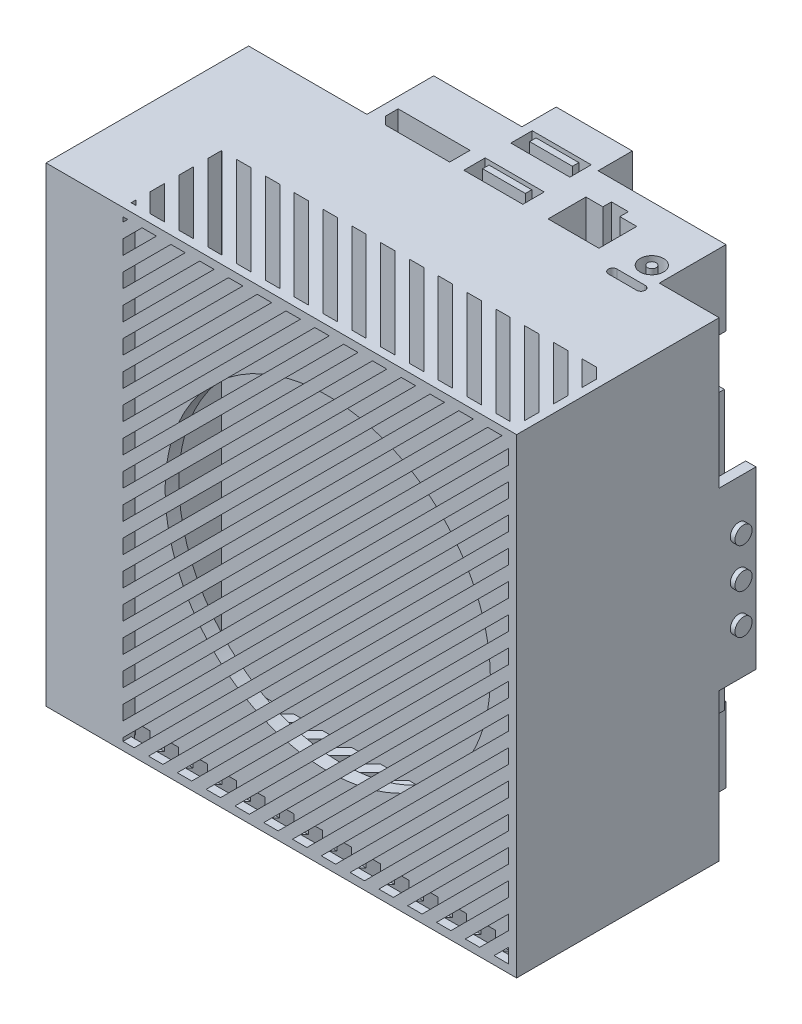
SolidWorks part; units mm, degrees
ref_plane "Plan de face" through (0, 0, 0) normal (0, 0, 1) x (1, 0, 0)
ref_plane "Plan de dessus" through (0, 0, 0) normal (0, 1, 0) x (1, 0, 0)
ref_plane "Plan de droite" through (0, 0, 0) normal (1, 0, 0) x (0, 0, -1)
sketch "Esquisse1" plane through (0, 0, 0) normal (0, 0, 1) x (1, 0, 0)
  line L0 (-110, 0) -> (0, 0)
  line L1 (0, 0) -> (0, -110)
  line L2 (0, -110) -> (-110, -110)
  line L3 (-110, -110) -> (-110, 0)
  line L4 (-107.6, -55) -> (-110, -55) construction
  line L5 (-107.6, -17.5) -> (-2.4, -17.5)
  line L6 (-107.6, -17.5) -> (-107.6, -92.5)
  line L7 (-107.6, -92.5) -> (-2.4, -92.5)
  line L8 (-2.4, -17.5) -> (-2.4, -92.5)
  line L9 (-2.4, -55) -> (0, -55) construction
  line L10 (-87.5, -9) -> (-87.5, 0) construction
  line L11 (-87.5, -101) -> (-87.5, -110) construction
  circle A0 centre (-87.5, -9) radius 3.1
  circle A1 centre (-8.5, -9) radius 3.1
  circle A2 centre (-87.5, -101) radius 3.1
  circle A3 centre (-8.5, -101) radius 3.1
  dimension "D7" = 6.2
  dimension "D1" = 110
  dimension "D2" = 2.4
  dimension "D3" = 17.5
  dimension "D4" = 9
  dimension "D5" = 8.5
  dimension "D6" = 79
extrude "Boss.-Extru.1" add sketch "Esquisse1" along normal blind 23.6
sketch "Esquisse3" plane through (0, 0, 23.6) normal (0, 0, 1) x (1, 0, 0)
  line L0 (0, -110) -> (0, 0) construction
  line L1 (-110, -110) -> (0, -110) construction
  line L2 (-110, 0) -> (-110, -110) construction
  line L3 (0, 0) -> (-110, 0) construction
  line L4 (0, -110) -> (0, 0)
  line L5 (-110, -110) -> (0, -110)
  line L6 (-110, 0) -> (-110, -110)
  line L7 (0, 0) -> (-110, 0)
extrude "Boss.-Extru.2" add sketch "Esquisse3" along normal blind 47.35
sketch "Esquisse15" plane through (0, 0, 23.6) normal (0, 0, -1) x (-1, 0, 0)
  circle A0 centre (87.5, -9) radius 1.25
  circle A1 centre (8.5, -9) radius 1.25
  circle A2 centre (8.5, -101) radius 1.25
  circle A3 centre (87.5, -101) radius 1.25
  dimension "D1" = 2.5
extrude "Enlèv. mat.-Extru.11" cut sketch "Esquisse15" against normal blind 10
sketch "Esquisse4" plane through (0, 0, 0) normal (0, 0, -1) x (-1, 0, 0)
  line L0 (0, -110) -> (0, 0) construction
  line L1 (0, -34.5) -> (2.4, -34.5)
  line L2 (0, -34.5) -> (0, -75.5)
  line L3 (0, -75.5) -> (2.4, -75.5)
  line L4 (2.4, -34.5) -> (2.4, -75.5)
  line L5 (2.4, -92.5) -> (2.4, -17.5) construction
  point P8 (2.4, -55)
  point P9 (0, -55)
  dimension "D1" = 41
extrude "Enlèv. mat.-Extru.1" cut sketch "Esquisse4" against normal blind 15
sketch "Esquisse5" plane through (0, 0, 0) normal (1, 0, 0) x (0, 0, -1)
  line L0 (-19, -45.7) -> (-19, -55) construction
  line L1 (-19, -55) -> (-19, -64.3) construction
  line L2 (-15, -34.5) -> (-15, -75.5) construction
  circle A0 centre (-19, -45.7) radius 2
  circle A1 centre (-19, -55) radius 2
  circle A2 centre (-19, -64.3) radius 2
  point P8 (-15, -55)
  dimension "D1" = 4
  dimension "D2" = 9.3
  dimension "D3" = 4
extrude "Boss.-Extru.3" add sketch "Esquisse5" along normal blind 1.1
sketch "Esquisse6" plane through (0, 0, 23.6) normal (0, 0, -1) x (-1, 0, 0)
  line L1 (7.4, -22.5) -> (102.6, -22.5)
  line L2 (7.4, -22.5) -> (7.4, -87.5)
  line L3 (7.4, -87.5) -> (102.6, -87.5)
  line L4 (102.6, -22.5) -> (102.6, -87.5)
  line L5 (55, -22.5) -> (55, -17.5) construction
  line L6 (2.4, -17.5) -> (107.6, -17.5) construction
  line L7 (102.6, -55) -> (107.6, -55) construction
  line L8 (107.6, -17.5) -> (107.6, -92.5) construction
  line L9 (2.4, -55) -> (7.4, -55) construction
  line L10 (2.4, -92.5) -> (2.4, -17.5) construction
  line L11 (55, -87.5) -> (55, -92.5) construction
  line L12 (107.6, -92.5) -> (2.4, -92.5) construction
  dimension "D1" = 5
extrude "Boss.-Extru.4" add sketch "Esquisse6" along normal up to surface (8.6 mm away) up to face at (-1.2, -55, 15)
sketch "Esquisse7" plane through (0, 0, 70.95) normal (0, 0, 1) x (1, 0, 0)
  line L0 (-1.9, -108.1) -> (-1.9, -110) construction
  line L1 (-1.9, -108.1) -> (-92, -108.1) construction
  line L2 (-1.9, -108.1) -> (-1.9, -1.9) construction
  line L3 (-1.9, -1.9) -> (-92, -1.9) construction
  line L4 (-92, -108.1) -> (-92, -1.9) construction
  line L5 (-110, -110) -> (0, -110) construction
  line L6 (-1.9, -108.1) -> (0, -108.1) construction
  line L7 (0, -110) -> (0, 0) construction
  line L8 (-1.9, -1.9) -> (-1.9, 0) construction
  line L9 (0, 0) -> (-110, 0) construction
  line L10 (-1.9, -1.9) -> (0, -1.9) construction
  line L11 (-110, 0) -> (-110, -110) construction
  line L12 (-1.9, -101.3683) -> (-8.6317, -108.1)
  line L13 (-1.9, -101.3683) -> (-1.9, -98.0025)
  line L14 (-1.9, -98.0025) -> (-11.9975, -108.1)
  line L15 (-11.9975, -108.1) -> (-8.6317, -108.1)
  line L16 (-1.9, -108.1) -> (-1.9, -104.7342)
  line L17 (-1.9, -104.7342) -> (-5.2658, -108.1)
  line L18 (-5.2658, -108.1) -> (-1.9, -108.1)
  line L19 (-1.9, -108.1) -> (-3.5829, -106.4171) construction
  line L20 (-3.5829, -106.4171) -> (-5.2658, -104.7342) construction
  line L21 (-5.2658, -104.7342) -> (-6.9487, -103.0513) construction
  line L22 (-6.9487, -103.0513) -> (-8.6317, -101.3683) construction
  line L23 (-8.6317, -101.3683) -> (-10.3146, -99.6854) construction
  line L24 (-1.9, -94.6367) -> (-15.3633, -108.1)
  line L25 (-15.3633, -108.1) -> (-18.7291, -108.1)
  line L26 (-18.7291, -108.1) -> (-1.9, -91.2709)
  line L27 (-1.9, -91.2709) -> (-1.9, -94.6367)
  line L28 (-1.9, -87.905) -> (-22.095, -108.1)
  line L29 (-22.095, -108.1) -> (-25.4608, -108.1)
  line L30 (-25.4608, -108.1) -> (-1.9, -84.5392)
  line L31 (-1.9, -84.5392) -> (-1.9, -87.905)
  line L32 (-1.9, -81.1734) -> (-28.8266, -108.1)
  line L33 (-28.8266, -108.1) -> (-32.1925, -108.1)
  line L34 (-32.1925, -108.1) -> (-1.9, -77.8075)
  line L35 (-1.9, -77.8075) -> (-1.9, -81.1734)
  line L36 (-1.9, -74.4417) -> (-35.5583, -108.1)
  line L37 (-35.5583, -108.1) -> (-38.9241, -108.1)
  line L38 (-38.9241, -108.1) -> (-1.9, -71.0759)
  line L39 (-1.9, -71.0759) -> (-1.9, -74.4417)
  line L40 (-1.9, -67.7101) -> (-42.2899, -108.1)
  line L41 (-42.2899, -108.1) -> (-45.6558, -108.1)
  line L42 (-45.6558, -108.1) -> (-1.9, -64.3442)
  line L43 (-1.9, -64.3442) -> (-1.9, -67.7101)
  line L44 (-1.9, -60.9784) -> (-49.0216, -108.1)
  line L45 (-49.0216, -108.1) -> (-52.3874, -108.1)
  line L46 (-52.3874, -108.1) -> (-1.9, -57.6126)
  line L47 (-1.9, -57.6126) -> (-1.9, -60.9784)
  line L48 (-1.9, -54.2467) -> (-55.7533, -108.1)
  line L49 (-55.7533, -108.1) -> (-59.1191, -108.1)
  line L50 (-59.1191, -108.1) -> (-1.9, -50.8809)
  line L51 (-1.9, -50.8809) -> (-1.9, -54.2467)
  line L52 (-10.3146, -99.6854) -> (-11.9975, -98.0025) construction
  line L53 (-11.9975, -98.0025) -> (-13.6804, -96.3196) construction
  line L54 (-13.6804, -96.3196) -> (-15.3633, -94.6367) construction
  line L55 (-15.3633, -94.6367) -> (-17.0462, -92.9538) construction
  line L56 (-17.0462, -92.9538) -> (-18.7291, -91.2709) construction
  line L57 (-18.7291, -91.2709) -> (-20.4121, -89.5879) construction
  line L58 (-20.4121, -89.5879) -> (-22.095, -87.905) construction
  line L59 (-22.095, -87.905) -> (-23.7779, -86.2221) construction
  line L60 (-23.7779, -86.2221) -> (-25.4608, -84.5392) construction
  line L61 (-25.4608, -84.5392) -> (-27.1437, -82.8563) construction
  line L62 (-27.1437, -82.8563) -> (-28.8266, -81.1734) construction
  line L63 (-28.8266, -81.1734) -> (-30.5095, -79.4905) construction
  line L64 (-1.9, -47.5151) -> (-62.4849, -108.1)
  line L65 (-62.4849, -108.1) -> (-65.8507, -108.1)
  line L66 (-65.8507, -108.1) -> (-1.9, -44.1493)
  line L67 (-1.9, -44.1493) -> (-1.9, -47.5151)
  line L68 (-69.2166, -108.1) -> (-1.9, -40.7834)
  line L69 (-1.9, -40.7834) -> (-1.9, -37.4176)
  line L70 (-1.9, -37.4176) -> (-72.5824, -108.1)
  line L71 (-72.5824, -108.1) -> (-69.2166, -108.1)
  line L72 (-1.9, -34.0518) -> (-75.9482, -108.1)
  line L73 (-75.9482, -108.1) -> (-79.3141, -108.1)
  line L74 (-79.3141, -108.1) -> (-1.9, -30.6859)
  line L75 (-1.9, -30.6859) -> (-1.9, -34.0518)
  line L76 (-82.6799, -108.1) -> (-86.0457, -108.1)
  line L77 (-86.0457, -108.1) -> (-1.9, -23.9543)
  line L78 (-1.9, -23.9543) -> (-1.9, -27.3201)
  line L79 (-1.9, -27.3201) -> (-82.6799, -108.1)
  line L81 (-92, -107.3226) -> (-1.9, -17.2226)
  line L82 (-1.9, -17.2226) -> (-1.9, -20.5885)
  line L83 (-1.9, -20.5885) -> (-89.4115, -108.1)
  line L84 (-92, -103.9568) -> (-92, -100.591)
  line L85 (-92, -100.591) -> (-1.9, -10.491)
  line L86 (-1.9, -10.491) -> (-1.9, -13.8568)
  line L87 (-1.9, -13.8568) -> (-92, -103.9568)
  line L88 (-30.5095, -79.4905) -> (-32.1925, -77.8075) construction
  line L89 (-32.1925, -77.8075) -> (-33.8754, -76.1246) construction
  line L90 (-33.8754, -76.1246) -> (-35.5583, -74.4417) construction
  line L91 (-35.5583, -74.4417) -> (-37.2412, -72.7588) construction
  line L92 (-37.2412, -72.7588) -> (-38.9241, -71.0759) construction
  line L93 (-38.9241, -71.0759) -> (-40.607, -69.393) construction
  line L94 (-40.607, -69.393) -> (-42.2899, -67.7101) construction
  line L95 (-42.2899, -67.7101) -> (-43.9729, -66.0271) construction
  line L96 (-43.9729, -66.0271) -> (-45.6558, -64.3442) construction
  line L97 (-45.6558, -64.3442) -> (-47.3387, -62.6613) construction
  line L98 (-47.3387, -62.6613) -> (-49.0216, -60.9784) construction
  line L99 (-49.0216, -60.9784) -> (-50.7045, -59.2955) construction
  line L100 (-89.4115, -108.1) -> (-92, -108.1)
  line L101 (-92, -108.1) -> (-92, -107.3226)
  line L102 (-92, -97.2252) -> (-1.9, -7.1252)
  line L103 (-1.9, -7.1252) -> (-1.9, -3.7593)
  line L104 (-1.9, -3.7593) -> (-92, -93.8593)
  line L105 (-92, -93.8593) -> (-92, -97.2252)
  line L106 (-50.7045, -59.2955) -> (-52.3874, -57.6126) construction
  line L107 (-52.3874, -57.6126) -> (-54.0703, -55.9297) construction
  line L108 (-92, -90.4935) -> (-3.4065, -1.9)
  line L109 (-3.4065, -1.9) -> (-6.7723, -1.9)
  line L110 (-6.7723, -1.9) -> (-92, -87.1277)
  line L111 (-92, -87.1277) -> (-92, -90.4935)
  line L112 (-92, -83.7618) -> (-10.1382, -1.9)
  line L113 (-10.1382, -1.9) -> (-13.504, -1.9)
  line L114 (-13.504, -1.9) -> (-92, -80.396)
  line L115 (-92, -80.396) -> (-92, -83.7618)
  line L116 (-92, -77.0302) -> (-16.8698, -1.9)
  line L117 (-16.8698, -1.9) -> (-20.2356, -1.9)
  line L118 (-20.2356, -1.9) -> (-92, -73.6644)
  line L119 (-92, -73.6644) -> (-92, -77.0302)
  line L120 (-92, -70.2985) -> (-23.6015, -1.9)
  line L121 (-23.6015, -1.9) -> (-26.9673, -1.9)
  line L122 (-26.9673, -1.9) -> (-92, -66.9327)
  line L123 (-92, -66.9327) -> (-92, -70.2985)
  line L124 (-92, -63.5669) -> (-30.3331, -1.9)
  line L125 (-30.3331, -1.9) -> (-33.699, -1.9)
  line L126 (-33.699, -1.9) -> (-92, -60.201)
  line L127 (-92, -60.201) -> (-92, -63.5669)
  line L128 (-92, -56.8352) -> (-37.0648, -1.9)
  line L129 (-37.0648, -1.9) -> (-40.4306, -1.9)
  line L130 (-40.4306, -1.9) -> (-92, -53.4694)
  line L131 (-92, -53.4694) -> (-92, -56.8352)
  line L132 (-92, -50.1036) -> (-43.7964, -1.9)
  line L133 (-43.7964, -1.9) -> (-47.1623, -1.9)
  line L134 (-47.1623, -1.9) -> (-92, -46.7377)
  line L135 (-92, -46.7377) -> (-92, -50.1036)
  line L136 (-54.0703, -55.9297) -> (-55.7533, -54.2467) construction
  line L137 (-55.7533, -54.2467) -> (-57.4362, -52.5638) construction
  line L138 (-57.4362, -52.5638) -> (-59.1191, -50.8809) construction
  line L139 (-59.1191, -50.8809) -> (-60.802, -49.198) construction
  line L140 (-60.802, -49.198) -> (-62.4849, -47.5151) construction
  line L141 (-62.4849, -47.5151) -> (-64.1678, -45.8322) construction
  line L142 (-64.1678, -45.8322) -> (-65.8507, -44.1493) construction
  line L143 (-65.8507, -44.1493) -> (-67.5337, -42.4663) construction
  line L144 (-67.5337, -42.4663) -> (-69.2166, -40.7834) construction
  line L145 (-69.2166, -40.7834) -> (-70.8995, -39.1005) construction
  line L146 (-70.8995, -39.1005) -> (-72.5824, -37.4176) construction
  line L147 (-72.5824, -37.4176) -> (-74.2653, -35.7347) construction
  line L148 (-74.2653, -35.7347) -> (-75.9482, -34.0518) construction
  line L149 (-75.9482, -34.0518) -> (-77.6311, -32.3689) construction
  line L150 (-92, -43.3719) -> (-50.5281, -1.9)
  line L151 (-50.5281, -1.9) -> (-53.8939, -1.9)
  line L152 (-53.8939, -1.9) -> (-92, -40.0061)
  line L153 (-92, -40.0061) -> (-92, -43.3719)
  line L154 (-92, -36.6402) -> (-57.2598, -1.9)
  line L155 (-57.2598, -1.9) -> (-60.6256, -1.9)
  line L156 (-60.6256, -1.9) -> (-92, -33.2744)
  line L157 (-92, -33.2744) -> (-92, -36.6402)
  line L158 (-92, -29.9086) -> (-63.9914, -1.9)
  line L159 (-63.9914, -1.9) -> (-67.3572, -1.9)
  line L160 (-67.3572, -1.9) -> (-92, -26.5428)
  line L161 (-92, -26.5428) -> (-92, -29.9086)
  line L162 (-92, -23.1769) -> (-70.7231, -1.9)
  line L163 (-70.7231, -1.9) -> (-74.0889, -1.9)
  line L164 (-74.0889, -1.9) -> (-92, -19.8111)
  line L165 (-92, -19.8111) -> (-92, -23.1769)
  line L166 (-92, -13.0794) -> (-80.8206, -1.9)
  line L167 (-80.8206, -1.9) -> (-77.4547, -1.9)
  line L168 (-77.4547, -1.9) -> (-92, -16.4453)
  line L169 (-92, -16.4453) -> (-92, -13.0794)
  line L170 (-92, -9.7136) -> (-84.1864, -1.9)
  line L171 (-84.1864, -1.9) -> (-87.5522, -1.9)
  line L172 (-87.5522, -1.9) -> (-92, -6.3478)
  line L173 (-92, -6.3478) -> (-92, -9.7136)
  line L174 (-77.6311, -32.3689) -> (-79.3141, -30.6859) construction
  line L175 (-79.3141, -30.6859) -> (-80.997, -29.003) construction
  line L176 (-80.997, -29.003) -> (-82.6799, -27.3201) construction
  line L177 (-82.6799, -27.3201) -> (-84.3628, -25.6372) construction
  line L178 (-84.3628, -25.6372) -> (-86.0457, -23.9543) construction
  line L179 (-86.0457, -23.9543) -> (-87.7286, -22.2714) construction
  line L180 (-79.6786, -14.2214) -> (-81.3615, -12.5385) construction
  line L181 (-81.3615, -12.5385) -> (-83.0444, -10.8556) construction
  line L182 (-83.0444, -10.8556) -> (-84.7274, -9.1726) construction
  line L183 (-84.7274, -9.1726) -> (-86.4103, -7.4897) construction
  line L184 (-86.4103, -7.4897) -> (-88.0932, -5.8068) construction
  line L185 (-88.0932, -5.8068) -> (-89.7761, -4.1239) construction
  line L186 (-92, -1.9) -> (-92, -2.982)
  line L187 (-92, -2.982) -> (-90.918, -1.9)
  line L188 (-90.918, -1.9) -> (-92, -1.9)
  line L189 (-92, -1.9) -> (-91.459, -2.441) construction
  line L190 (-91.459, -2.441) -> (-89.7761, -4.1239) construction
  point P32 (-8.6317, -101.3683)
  point P34 (-10.3146, -99.6854)
  dimension "D1" = 1.9
  dimension "D2" = 18
  dimension "D3" = 45
  dimension "D4" = 2.38
extrude "Enlèv. mat.-Extru.2" cut sketch "Esquisse7" against normal blind 2.8
sketch "Esquisse8" plane through (0, 0, 68.15) normal (0, 0, 1) x (1, 0, 0)
  line L2 (0, -110) -> (0, 0) construction
  circle A0 centre (-46.95, -55) radius 38
  point P3 (0, -55)
  dimension "D1" = 76
  dimension "D2" = 46.95
extrude "Enlèv. mat.-Extru.3" cut sketch "Esquisse8" against normal blind 20.14
sketch "Esquisse9" plane through (0, 0, 0) normal (0, 1, 0) x (1, 0, 0)
  line L0 (-1.9, -69.05) -> (-1.9, -47.95) construction
  line L1 (-1.9, -47.95) -> (-92, -47.95) construction
  line L2 (-92, -47.95) -> (-92, -69.05) construction
  line L3 (-92, -69.05) -> (-1.9, -69.05) construction
  line L4 (0, -70.95) -> (-110, -70.95) construction
  line L5 (-1.9, -69.05) -> (0, -69.05) construction
  line L6 (0, -70.95) -> (0, 0) construction
  line L7 (-1.9, -69.05) -> (-1.9, -70.95) construction
  line L8 (-84.1864, -70.95) -> (-87.5522, -70.95) construction
  line L9 (-77.4547, -70.95) -> (-80.8206, -70.95) construction
  line L10 (-70.7231, -70.95) -> (-74.0889, -70.95) construction
  line L11 (-63.9914, -70.95) -> (-67.3572, -70.95) construction
  line L12 (-57.2598, -70.95) -> (-60.6256, -70.95) construction
  line L13 (-50.5281, -70.95) -> (-53.8939, -70.95) construction
  line L14 (-43.7964, -70.95) -> (-47.1623, -70.95) construction
  line L15 (-37.0648, -70.95) -> (-40.4306, -70.95) construction
  line L16 (-30.3331, -70.95) -> (-33.699, -70.95) construction
  line L17 (-23.6015, -70.95) -> (-26.9673, -70.95) construction
  line L18 (-16.8698, -70.95) -> (-20.2356, -70.95) construction
  line L19 (-10.1382, -70.95) -> (-13.504, -70.95) construction
  line L20 (-3.4065, -70.95) -> (-6.7723, -70.95) construction
  line L21 (-84.1864, -70.95) -> (-87.5522, -70.95) construction
  line L22 (-77.4547, -70.95) -> (-80.8206, -70.95) construction
  line L23 (-70.7231, -70.95) -> (-74.0889, -70.95) construction
  line L24 (-63.9914, -70.95) -> (-67.3572, -70.95) construction
  line L25 (-57.2598, -70.95) -> (-60.6256, -70.95) construction
  line L26 (-50.5281, -70.95) -> (-53.8939, -70.95) construction
  line L27 (-43.7964, -70.95) -> (-47.1623, -70.95) construction
  line L28 (-37.0648, -70.95) -> (-40.4306, -70.95) construction
  line L29 (-30.3331, -70.95) -> (-33.699, -70.95) construction
  line L30 (-23.6015, -70.95) -> (-26.9673, -70.95) construction
  line L31 (-16.8698, -70.95) -> (-20.2356, -70.95) construction
  line L32 (-10.1382, -70.95) -> (-13.504, -70.95) construction
  line L33 (-3.4065, -70.95) -> (-6.7723, -70.95) construction
  line L34 (-3.4065, -69.05) -> (-24.5065, -47.95)
  line L35 (-24.5065, -47.95) -> (-27.8723, -47.95)
  line L36 (-27.8723, -47.95) -> (-6.7723, -69.05)
  line L37 (-6.7723, -69.05) -> (-3.4065, -69.05)
  line L38 (-10.1382, -69.05) -> (-31.2382, -47.95)
  line L39 (-31.2382, -47.95) -> (-34.604, -47.95)
  line L40 (-34.604, -47.95) -> (-13.504, -69.05)
  line L41 (-13.504, -69.05) -> (-10.1382, -69.05)
  line L42 (-16.8698, -69.05) -> (-37.9698, -47.95)
  line L43 (-37.9698, -47.95) -> (-41.3356, -47.95)
  line L44 (-41.3356, -47.95) -> (-20.2356, -69.05)
  line L45 (-20.2356, -69.05) -> (-16.8698, -69.05)
  line L50 (-23.6015, -69.05) -> (-44.7015, -47.95)
  line L51 (-44.7015, -47.95) -> (-48.0673, -47.95)
  line L52 (-48.0673, -47.95) -> (-26.9673, -69.05)
  line L53 (-26.9673, -69.05) -> (-23.6015, -69.05)
  line L54 (-30.3331, -69.05) -> (-51.4331, -47.95)
  line L55 (-51.4331, -47.95) -> (-54.799, -47.95)
  line L56 (-54.799, -47.95) -> (-33.699, -69.05)
  line L57 (-33.699, -69.05) -> (-30.3331, -69.05)
  line L58 (-37.0648, -69.05) -> (-58.1648, -47.95)
  line L59 (-58.1648, -47.95) -> (-61.5306, -47.95)
  line L60 (-61.5306, -47.95) -> (-40.4306, -69.05)
  line L61 (-40.4306, -69.05) -> (-37.0648, -69.05)
  line L62 (-43.7964, -69.05) -> (-64.8964, -47.95)
  line L63 (-64.8964, -47.95) -> (-68.2623, -47.95)
  line L64 (-68.2623, -47.95) -> (-47.1623, -69.05)
  line L65 (-47.1623, -69.05) -> (-43.7964, -69.05)
  line L66 (-50.5281, -69.05) -> (-71.6281, -47.95)
  line L67 (-71.6281, -47.95) -> (-74.9939, -47.95)
  line L68 (-74.9939, -47.95) -> (-53.8939, -69.05)
  line L69 (-53.8939, -69.05) -> (-50.5281, -69.05)
  line L70 (-57.2598, -69.05) -> (-78.3598, -47.95)
  line L71 (-78.3598, -47.95) -> (-81.7256, -47.95)
  line L72 (-81.7256, -47.95) -> (-60.6256, -69.05)
  line L73 (-60.6256, -69.05) -> (-57.2598, -69.05)
  line L74 (-63.9914, -69.05) -> (-85.0914, -47.95)
  line L75 (-85.0914, -47.95) -> (-88.4572, -47.95)
  line L76 (-88.4572, -47.95) -> (-67.3572, -69.05)
  line L77 (-67.3572, -69.05) -> (-63.9914, -69.05)
  line L78 (-70.7231, -69.05) -> (-91.8231, -47.95)
  line L80 (-92, -51.1389) -> (-74.0889, -69.05)
  line L81 (-74.0889, -69.05) -> (-70.7231, -69.05)
  line L82 (-77.4547, -69.05) -> (-92, -54.5047)
  line L83 (-92, -54.5047) -> (-92, -57.8706)
  line L84 (-92, -57.8706) -> (-80.8206, -69.05)
  line L85 (-80.8206, -69.05) -> (-77.4547, -69.05)
  line L86 (-84.1864, -69.05) -> (-92, -61.2364)
  line L87 (-92, -61.2364) -> (-92, -64.6022)
  line L88 (-92, -64.6022) -> (-87.5522, -69.05)
  line L89 (-87.5522, -69.05) -> (-84.1864, -69.05)
  line L90 (-92, -51.1389) -> (-92, -47.95)
  line L91 (-92, -47.95) -> (-91.8231, -47.95)
  line L92 (-92, -69.05) -> (-92, -67.968)
  line L93 (-92, -67.968) -> (-90.918, -69.05)
  line L94 (-90.918, -69.05) -> (-92, -69.05)
  line L95 (-90.918, -70.95) -> (-92, -70.95) construction
  line L96 (-90.918, -70.95) -> (-92, -70.95) construction
  line L97 (-1.9, -67.1907) -> (-21.1407, -47.95)
  line L98 (-21.1407, -47.95) -> (-17.7748, -47.95)
  line L99 (-17.7748, -47.95) -> (-1.9, -63.8248)
  line L100 (-1.9, -63.8248) -> (-1.9, -67.1907)
  line L101 (-1.9, -60.459) -> (-14.409, -47.95)
  line L102 (-14.409, -47.95) -> (-11.0432, -47.95)
  line L103 (-11.0432, -47.95) -> (-1.9, -57.0932)
  line L104 (-1.9, -57.0932) -> (-1.9, -60.459)
  line L105 (-1.9, -53.7274) -> (-7.6774, -47.95)
  line L106 (-7.6774, -47.95) -> (-4.3115, -47.95)
  line L107 (-4.3115, -47.95) -> (-1.9, -50.3615)
  line L108 (-1.9, -50.3615) -> (-1.9, -53.7274)
  line L109 (-13.2033, -59.2533) -> (-11.5203, -57.5703) construction
  line L110 (-11.5203, -57.5703) -> (-9.8374, -55.8874) construction
  line L111 (-9.8374, -55.8874) -> (-8.1545, -54.2045) construction
  line L112 (-8.1545, -54.2045) -> (-6.4716, -52.5216) construction
  line L113 (-6.4716, -52.5216) -> (-4.7887, -50.8387) construction
  line L114 (-4.7887, -50.8387) -> (-3.1058, -49.1558) construction
  line L115 (-13.2033, -59.2533) -> (-14.8862, -60.9362) construction
  line L116 (-1.9, -47.95) -> (-3.1058, -49.1558) construction
  dimension "D1" = 23
  dimension "D2" = 45
extrude "Enlèv. mat.-Extru.4" cut sketch "Esquisse9" against normal blind 4.4
sketch "Esquisse10" plane through (0, -110, 0) normal (0, -1, 0) x (1, 0, 0)
  line L0 (-92, 70.95) -> (-89.4115, 70.95) construction
  line L1 (-92, 69.05) -> (-1.9, 69.05) construction
  line L2 (-92, 69.05) -> (-92, 47.95) construction
  line L3 (-92, 47.95) -> (-1.9, 47.95) construction
  line L4 (-1.9, 69.05) -> (-1.9, 47.95) construction
  line L5 (-86.0457, 70.95) -> (-82.6799, 70.95) construction
  line L6 (-79.3141, 70.95) -> (-75.9482, 70.95) construction
  line L7 (-72.5824, 70.95) -> (-69.2166, 70.95) construction
  line L8 (-65.8507, 70.95) -> (-62.4849, 70.95) construction
  line L9 (-59.1191, 70.95) -> (-55.7533, 70.95) construction
  line L10 (-52.3874, 70.95) -> (-49.0216, 70.95) construction
  line L11 (-45.6558, 70.95) -> (-42.2899, 70.95) construction
  line L12 (-38.9241, 70.95) -> (-35.5583, 70.95) construction
  line L13 (-32.1925, 70.95) -> (-28.8266, 70.95) construction
  line L14 (-25.4608, 70.95) -> (-22.095, 70.95) construction
  line L15 (-18.7291, 70.95) -> (-15.3633, 70.95) construction
  line L16 (-11.9975, 70.95) -> (-8.6317, 70.95) construction
  line L17 (-5.2658, 70.95) -> (-1.9, 70.95) construction
  line L18 (-92, 70.95) -> (-89.4115, 70.95) construction
  line L19 (-86.0457, 70.95) -> (-82.6799, 70.95) construction
  line L20 (-79.3141, 70.95) -> (-75.9482, 70.95) construction
  line L21 (-72.5824, 70.95) -> (-69.2166, 70.95) construction
  line L22 (-65.8507, 70.95) -> (-62.4849, 70.95) construction
  line L23 (-59.1191, 70.95) -> (-55.7533, 70.95) construction
  line L24 (-52.3874, 70.95) -> (-49.0216, 70.95) construction
  line L25 (-45.6558, 70.95) -> (-42.2899, 70.95) construction
  line L26 (-38.9241, 70.95) -> (-35.5583, 70.95) construction
  line L27 (-32.1925, 70.95) -> (-28.8266, 70.95) construction
  line L28 (-25.4608, 70.95) -> (-22.095, 70.95) construction
  line L29 (-18.7291, 70.95) -> (-15.3633, 70.95) construction
  line L30 (-11.9975, 70.95) -> (-8.6317, 70.95) construction
  line L31 (-5.2658, 70.95) -> (-1.9, 70.95) construction
  line L32 (-24.5065, 47.95) -> (-27.8723, 47.95) construction
  line L33 (0, 69.05) -> (-1.9, 69.05) construction
  line L34 (0, 70.95) -> (0, 0) construction
  line L35 (-1.9, 69.05) -> (-1.9, 70.95) construction
  line L36 (-1.9, 69.05) -> (-5.2658, 69.05)
  line L37 (-5.2658, 69.05) -> (-1.9, 65.6842)
  line L38 (-1.9, 65.6842) -> (-1.9, 69.05)
  line L39 (-11.9975, 69.05) -> (-1.9, 58.9525)
  line L40 (-1.9, 58.9525) -> (-1.9, 62.3183)
  line L41 (-1.9, 62.3183) -> (-8.6317, 69.05)
  line L42 (-8.6317, 69.05) -> (-11.9975, 69.05)
  line L43 (-18.7291, 69.05) -> (-1.9, 52.2209)
  line L44 (-1.9, 52.2209) -> (-1.9, 55.5867)
  line L45 (-1.9, 55.5867) -> (-15.3633, 69.05)
  line L46 (-15.3633, 69.05) -> (-18.7291, 69.05)
  line L47 (-22.095, 69.05) -> (-1.9, 48.855)
  line L49 (-4.3608, 47.95) -> (-25.4608, 69.05)
  line L50 (-25.4608, 69.05) -> (-22.095, 69.05)
  line L51 (-1.9, 48.855) -> (-1.9, 47.95)
  line L52 (-1.9, 47.95) -> (-4.3608, 47.95)
  line L53 (-28.8266, 69.05) -> (-7.7266, 47.95)
  line L54 (-7.7266, 47.95) -> (-11.0925, 47.95)
  line L55 (-11.0925, 47.95) -> (-32.1925, 69.05)
  line L56 (-32.1925, 69.05) -> (-28.8266, 69.05)
  line L57 (-35.5583, 69.05) -> (-14.4583, 47.95)
  line L58 (-14.4583, 47.95) -> (-17.8241, 47.95)
  line L59 (-17.8241, 47.95) -> (-38.9241, 69.05)
  line L60 (-38.9241, 69.05) -> (-35.5583, 69.05)
  line L61 (-42.2899, 69.05) -> (-21.1899, 47.95)
  line L62 (-21.1899, 47.95) -> (-24.5558, 47.95)
  line L63 (-24.5558, 47.95) -> (-45.6558, 69.05)
  line L64 (-45.6558, 69.05) -> (-42.2899, 69.05)
  line L65 (-49.0216, 69.05) -> (-27.9216, 47.95)
  line L66 (-27.9216, 47.95) -> (-31.2874, 47.95)
  line L67 (-31.2874, 47.95) -> (-52.3874, 69.05)
  line L68 (-52.3874, 69.05) -> (-49.0216, 69.05)
  line L69 (-55.7533, 69.05) -> (-34.6533, 47.95)
  line L70 (-34.6533, 47.95) -> (-38.0191, 47.95)
  line L71 (-38.0191, 47.95) -> (-59.1191, 69.05)
  line L72 (-59.1191, 69.05) -> (-55.7533, 69.05)
  line L73 (-62.4849, 69.05) -> (-41.3849, 47.95)
  line L74 (-41.3849, 47.95) -> (-44.7507, 47.95)
  line L75 (-44.7507, 47.95) -> (-65.8507, 69.05)
  line L76 (-65.8507, 69.05) -> (-62.4849, 69.05)
  line L77 (-69.2166, 69.05) -> (-48.1166, 47.95)
  line L78 (-48.1166, 47.95) -> (-51.4824, 47.95)
  line L79 (-51.4824, 47.95) -> (-72.5824, 69.05)
  line L80 (-72.5824, 69.05) -> (-69.2166, 69.05)
  line L81 (-75.9482, 69.05) -> (-54.8482, 47.95)
  line L82 (-54.8482, 47.95) -> (-58.2141, 47.95)
  line L83 (-58.2141, 47.95) -> (-79.3141, 69.05)
  line L84 (-79.3141, 69.05) -> (-75.9482, 69.05)
  line L85 (-82.6799, 69.05) -> (-61.5799, 47.95)
  line L86 (-61.5799, 47.95) -> (-64.9457, 47.95)
  line L87 (-64.9457, 47.95) -> (-86.0457, 69.05)
  line L88 (-86.0457, 69.05) -> (-82.6799, 69.05)
  line L90 (-71.6774, 47.95) -> (-92, 68.2726)
  line L91 (-92, 68.2726) -> (-92, 69.05)
  line L92 (-92, 69.05) -> (-89.4115, 69.05)
  line L93 (-89.4115, 69.05) -> (-68.3115, 47.95)
  line L94 (-68.3115, 47.95) -> (-71.6774, 47.95)
  line L95 (-92, 64.9068) -> (-75.0432, 47.95)
  line L96 (-75.0432, 47.95) -> (-78.409, 47.95)
  line L97 (-78.409, 47.95) -> (-92, 61.541)
  line L98 (-92, 61.541) -> (-92, 64.9068)
  line L99 (-92, 58.1752) -> (-81.7748, 47.95)
  line L100 (-81.7748, 47.95) -> (-85.1407, 47.95)
  line L101 (-85.1407, 47.95) -> (-92, 54.8093)
  line L102 (-92, 54.8093) -> (-92, 58.1752)
  line L105 (-88.5065, 47.95) -> (-92, 51.4435)
  line L107 (-79.2697, 65.6398) -> (-80.9526, 63.9569) construction
  line L108 (-80.9526, 63.9569) -> (-82.6356, 62.274) construction
  line L109 (-82.6356, 62.274) -> (-84.3185, 60.5911) construction
  line L110 (-84.3185, 60.5911) -> (-86.0014, 58.9082) construction
  line L111 (-86.0014, 58.9082) -> (-87.6843, 57.2253) construction
  line L112 (-87.6843, 57.2253) -> (-89.3672, 55.5424) construction
  line L113 (-89.3672, 55.5424) -> (-91.0501, 53.8594) construction
  line L114 (-91.0501, 53.8594) -> (-92.733, 52.1765) construction
  line L115 (-92, 51.4435) -> (-92, 47.95)
  line L116 (-92, 47.95) -> (-88.5065, 47.95)
  dimension "D1" = 45
extrude "Enlèv. mat.-Extru.5" cut sketch "Esquisse10" against normal blind 4.4
sketch "Esquisse11" plane through (0, -105.6, 0) normal (0, -1, 0) x (1, 0, 0)
  line L0 (-92, 64.9068) -> (-92, 61.541) construction
  line L1 (-92, 64.95) -> (-1.9, 64.95)
  line L2 (-92, 64.95) -> (-92, 47.95)
  line L3 (-92, 47.95) -> (-1.9, 47.95)
  line L4 (-1.9, 64.95) -> (-1.9, 47.95)
  line L5 (-1.9, 58.9525) -> (-1.9, 62.3183) construction
  line L7 (-11.0925, 47.95) -> (-7.7266, 47.95) construction
  line L10 (-110, 70.95) -> (0, 70.95) construction
  dimension "D1" = 6
extrude "Enlèv. mat.-Extru.7" cut sketch "Esquisse11" against normal up to surface (101.2 mm away) up to face at (-12.5451, -4.4, 61.7167)
sketch "Esquisse12" plane through (0, -110, 0) normal (0, -1, 0) x (1, 0, 0)
  line L3 (-28.2, 7.33) -> (-13.7, 7.33)
  line L4 (-13.7, 23.6) -> (-13.7, 7.33)
  line L5 (-106.8, 20.05) -> (-97.2, 20.05)
  line L6 (-106.8, 20.05) -> (-106.8, 23.6)
  line L7 (-106.8, 23.6) -> (-97.2, 23.6)
  line L8 (-97.2, 20.05) -> (-97.2, 23.6)
  line L9 (-82.33, 23.6) -> (-13.7, 23.6)
  line L10 (-82.33, 23.6) -> (-82.33, 17.05)
  line L11 (-82.33, 17.05) -> (-28.2, 17.05)
  line L13 (-110, 70.95) -> (-110, 0) construction
  line L14 (-110, 0) -> (0, 0) construction
  line L15 (-105.3, 21.825) -> (-98.7, 21.825) construction
  line L16 (-105.3, 22.825) -> (-98.7, 22.825)
  line L17 (-105.3, 20.825) -> (-98.7, 20.825)
  line L18 (-20.95, 17.33) -> (-20.95, 16.33) construction
  line L19 (-27.2, 21.33) -> (-14.7, 21.33)
  line L20 (-27.2, 21.33) -> (-27.2, 16.33)
  line L21 (-27.2, 16.33) -> (-14.7, 16.33)
  line L22 (-14.7, 21.33) -> (-14.7, 16.33)
  line L23 (-27.2, 13.33) -> (-14.7, 13.33)
  line L24 (-27.2, 13.33) -> (-27.2, 8.33)
  line L25 (-27.2, 8.33) -> (-14.7, 8.33)
  line L26 (-14.7, 13.33) -> (-14.7, 8.33)
  line L27 (-25.95, 18.83) -> (-15.95, 18.83)
  line L28 (-25.95, 18.83) -> (-25.95, 17.33)
  line L29 (-25.95, 17.33) -> (-15.95, 17.33)
  line L30 (-15.95, 18.83) -> (-15.95, 17.33)
  line L31 (-25.95, 10.83) -> (-15.95, 10.83)
  line L32 (-25.95, 10.83) -> (-25.95, 9.33)
  line L33 (-25.95, 9.33) -> (-15.95, 9.33)
  line L34 (-15.95, 10.83) -> (-15.95, 9.33)
  line L35 (-20.95, 9.33) -> (-20.95, 8.33) construction
  line L36 (-28.2, 17.05) -> (-28.2, 23.6)
  line L45 (-28.2, 7.33) -> (-28.2, 17.05)
  arc A0 (-105.3, 22.825) -> (-105.3, 20.825) centre (-105.3, 21.825) ccw
  arc A1 (-98.7, 20.825) -> (-98.7, 22.825) centre (-98.7, 21.825) ccw
  point P16 (-102, 21.825)
  point P23 (-106.8, 21.825)
  point P25 (-102, 23.6)
  point P39 (-20.95, 8.33)
  point P40 (-20.95, 7.33)
  point P41 (-20.95, 9.33)
  point P42 (-20.95, 17.33)
  point P43 (-20.95, 16.33)
  dimension "D11" = 1
  dimension "D1" = 3.2
  dimension "D2" = 12.8
  dimension "D3" = 27.67
  dimension "D4" = 81.8
  dimension "D5" = 96.3
  dimension "D6" = 23.6
  dimension "D7" = 3.55
  dimension "D8" = 6.55
  dimension "D9" = 16.27
  dimension "D10" = 1.5
  dimension "D13" = 3
  dimension "D14" = 10
  dimension "D15" = 1.5
  dimension "D16" = 5
  dimension "D17" = 1
  dimension "D18" = 1
extrude "Enlèv. mat.-Extru.8" cut sketch "Esquisse12" against normal blind 10 contours L11 L36 L9 L10 | L22 L19 L20 L21 L27 L30 L29 L28 | L26 L23 L24 L25 L31 L34 L33 L32 | L17 A1 L16 A0 region at (-55.265, -110, 20.325) region at (-102, -110, 21.825) region at (-20.95, -110, 19.0668) region at (-20.95, -110, 11.0668)
sketch "Esquisse13" plane through (0, 0, 0) normal (0, 1, 0) x (1, 0, 0)
  line L0 (0, -70.95) -> (0, 0) construction
  line L1 (-28.11, -23.6) -> (-40, -23.6)
  line L2 (-40, -23.6) -> (-40, -14.75)
  line L3 (-40, -14.75) -> (-36.0367, -14.75)
  line L4 (-36.0367, -14.75) -> (-36.0367, -12.75)
  line L5 (-36.0367, -12.75) -> (-32.0733, -12.75)
  line L6 (-32.0733, -12.75) -> (-32.0733, -14.75)
  line L7 (-32.0733, -14.75) -> (-28.11, -14.75)
  line L8 (-28.11, -14.75) -> (-28.11, -23.6)
  line L9 (0, 0) -> (-110, 0) construction
  line L10 (-63, -23.6) -> (-78.04, -23.6)
  line L11 (-45.9, -23.6) -> (-59.7, -23.6)
  line L12 (-45.9, -23.6) -> (-45.9, -18.6)
  line L13 (-45.9, -18.6) -> (-59.7, -18.6)
  line L14 (-59.7, -23.6) -> (-59.7, -18.6)
  line L15 (-45.9, -12.6) -> (-59.7, -12.6)
  line L16 (-45.9, -12.6) -> (-45.9, -7.6)
  line L17 (-45.9, -7.6) -> (-59.7, -7.6)
  line L18 (-59.7, -12.6) -> (-59.7, -7.6)
  line L19 (-78.04, -23.6) -> (-79.8, -21.84)
  line L20 (-79.8, -21.84) -> (-79.8, -18.84)
  line L21 (-79.8, -18.84) -> (-63, -18.84)
  line L22 (-63, -18.84) -> (-63, -23.6)
  line L23 (-15.19, -26.7) -> (-21.79, -26.7) construction
  line L24 (-15.19, -27.7) -> (-21.79, -27.7)
  line L25 (-15.19, -25.7) -> (-21.79, -25.7)
  line L26 (-105.3, -22.825) -> (-98.7, -22.825) construction
  line L27 (-27.2, -21.33) -> (-27.2, -16.33) construction
  line L28 (-47.8, -21.1) -> (-57.8, -21.1)
  line L29 (-47.8, -21.1) -> (-47.8, -19.6)
  line L30 (-47.8, -19.6) -> (-57.8, -19.6)
  line L31 (-57.8, -21.1) -> (-57.8, -19.6)
  line L32 (-47.8, -10.1) -> (-57.8, -10.1)
  line L33 (-47.8, -10.1) -> (-47.8, -8.6)
  line L34 (-47.8, -8.6) -> (-57.8, -8.6)
  line L35 (-57.8, -10.1) -> (-57.8, -8.6)
  line L36 (-25.95, -10.83) -> (-25.95, -9.33) construction
  line L37 (-25.95, -18.83) -> (-25.95, -17.33) construction
  line L38 (-25.95, -18.83) -> (-15.95, -18.83) construction
  circle A0 centre (-18.49, -20.85) radius 2.75
  circle A1 centre (-18.49, -20.85) radius 1
  arc A2 (-15.19, -27.7) -> (-15.19, -25.7) centre (-15.19, -26.7) ccw
  arc A3 (-21.79, -25.7) -> (-21.79, -27.7) centre (-21.79, -26.7) ccw
  arc A4 (-98.7, -22.825) -> (-98.7, -20.825) centre (-98.7, -21.825) ccw construction
  point P23 (-45.9, -10.1)
  point P30 (-18.49, -26.7)
  point P49 (-52.8, -8.6)
  point P50 (-52.8, -7.6)
  point P51 (-52.8, -19.6)
  point P52 (-52.8, -18.6)
  point P53 (-45.9, -14.8068)
  point P54 (-47.7699, -8.6788)
  point P55 (-47.5304, -11.0414)
  point P56 (-45.9, -12.75)
  point P63 (-63, -18.6)
  point P64 (-59.7, -18.84)
  point P65 (-59.7, -12.6)
  point P66 (-58.5169, -10.1)
  point P69 (-32.0733, -14.0736)
  dimension "D1" = 2
  dimension "D2" = 5.5
  dimension "D3" = 18.49
  dimension "D4" = 28.11
  dimension "D5" = 40
  dimension "D6" = 23.6
  dimension "D7" = 45.9
  dimension "D8" = 59.7
  dimension "D9" = 63
  dimension "D10" = 79.8
  dimension "D11" = 135
  dimension "D12" = 10.85
  dimension "D13" = 4.76
  dimension "D14" = 3
  dimension "D15" = 3.1
  dimension "D16" = 16
  dimension "D17" = 2
  dimension "D18" = 1
  dimension "D19" = 1
extrude "Enlèv. mat.-Extru.9" cut sketch "Esquisse13" against normal blind 10
sketch "Esquisse14" plane through (0, 0, 0) normal (0, 0, -1) x (-1, 0, 0)
  line L0 (0, -110) -> (14, -110)
  line L1 (110, -110) -> (0, -110) construction
  line L2 (14, -110) -> (14, -92.5)
  line L3 (107.6, -92.5) -> (2.4, -92.5) construction
  line L4 (14, -92.5) -> (2.4, -92.5)
  line L5 (2.4, -92.5) -> (2.4, -75.5)
  line L6 (2.4, -75.5) -> (0, -75.5)
  line L7 (0, -75.5) -> (0, -110)
  line L8 (0, -34.5) -> (2.4, -34.5)
  line L9 (82.33, -92.5) -> (92.33, -92.5)
  line L10 (82.33, -92.5) -> (82.33, -110)
  line L11 (82.33, -110) -> (92.33, -110)
  line L12 (92.33, -92.5) -> (92.33, -110)
  line L13 (2.4, -34.5) -> (2.4, -17.5)
  line L14 (2.4, -17.5) -> (14, -17.5)
  line L15 (2.4, -17.5) -> (107.6, -17.5) construction
  line L16 (14, -17.5) -> (14, 0)
  line L17 (0, 0) -> (110, 0) construction
  line L18 (14, 0) -> (0, 0)
  line L19 (0, 0) -> (0, -34.5)
  line L20 (110, 0) -> (110, -110) construction
  line L22 (82.33, -17.5) -> (82.33, 0)
  line L23 (82.33, 0) -> (110, 0)
  line L24 (110, -92.5) -> (110, 0)
  line L25 (107.6, -92.5) -> (110, -92.5)
  line L26 (107.6, -92.5) -> (107.6, -17.5)
  line L27 (107.6, -17.5) -> (82.33, -17.5)
  dimension "D1" = 10
  dimension "D2" = 14
extrude "Enlèv. mat.-Extru.10" cut sketch "Esquisse14" against normal up to surface (23.6 mm away) up to face at (-55, -55, 23.6)
sketch "Esquisse16" plane through (0, 0, 0) normal (0, 0, -1) x (-1, 0, 0)
  line L0 (14, -17.5) -> (82.33, -17.5) construction
  line L1 (82.33, -17.5) -> (61.7, -17.5)
  line L2 (82.33, -17.5) -> (82.33, 0.7323)
  line L3 (82.33, 0.7323) -> (61.7, 0.7323)
  line L4 (61.7, -17.5) -> (61.7, 0.7323)
  line L5 (14, 0) -> (43.9, 0)
  line L6 (14, 0) -> (14, -17.5)
  line L7 (14, -17.5) -> (43.9, -17.5)
  line L8 (43.9, 0) -> (43.9, -17.5)
  line L9 (82.33, -92.5) -> (82.33, -110) construction
  line L10 (14, -110) -> (82.33, -110)
  line L11 (14, -110) -> (14, -92.5)
  line L12 (14, -92.5) -> (82.33, -92.5)
  line L13 (82.33, -110) -> (82.33, -92.5)
  line L14 (82.33, -92.5) -> (14, -92.5) construction
  dimension "D1" = 2
  dimension "D2" = 2
extrude "Enlèv. mat.-Extru.12" cut sketch "Esquisse16" against normal blind 8
sketch "Esquisse17" plane through (0, 0, 0) normal (0, 0, -1) x (-1, 0, 0)
  line L0 (110, -92.5) -> (110, -110) construction
  line L1 (92.33, -110) -> (110, -110)
  line L2 (92.33, -110) -> (92.33, -92.5)
  line L3 (92.33, -92.5) -> (110, -92.5)
  line L4 (110, -110) -> (110, -92.5)
  line L5 (110, -92.5) -> (92.33, -92.5) construction
  point P7 (110, -95.1105)
extrude "Enlèv. mat.-Extru.13" cut sketch "Esquisse17" against normal blind 17
